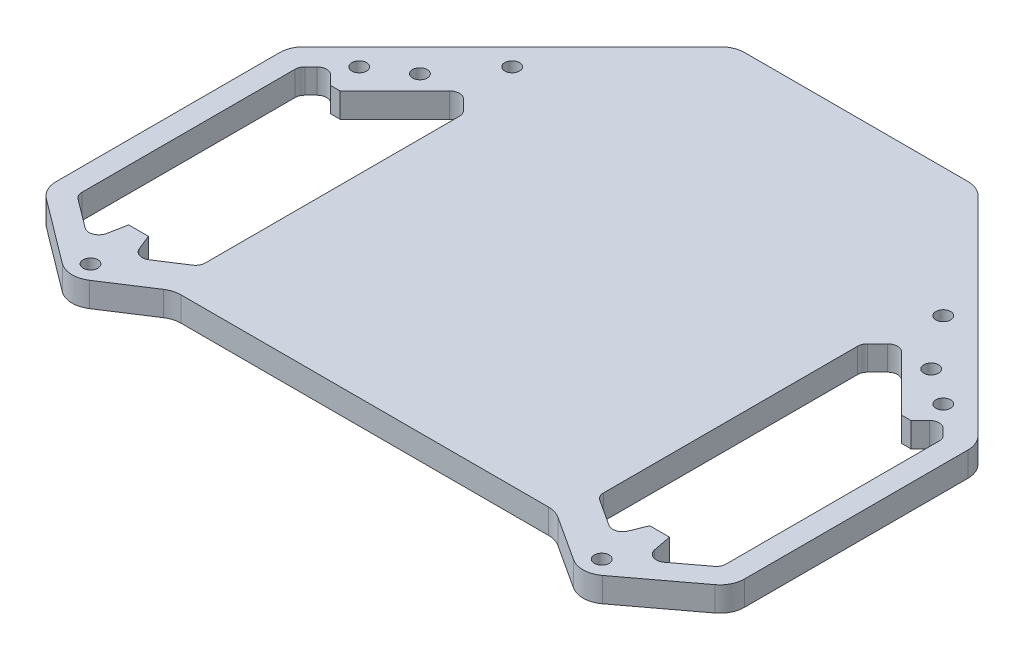
SolidWorks part; units mm, degrees
ref_plane "Front Plane" through (0, 0, 0) normal (0, 0, 1) x (1, 0, 0)
ref_plane "Top Plane" through (0, 0, 0) normal (0, 1, 0) x (1, 0, 0)
ref_plane "Right Plane" through (0, 0, 0) normal (1, 0, 0) x (0, 0, -1)
sketch "Sketch1" plane through (0, 0, 0) normal (0, 1, 0) x (1, 0, 0)
  line L0 (-52.1641, -38.6452) -> (-70, -25.2479)
  line L1 (-70, -25.2479) -> (-70, 24.7523)
  line L2 (-70, 24.7523) -> (-24.7523, 70)
  line L3 (-52.1641, -38.6452) -> (-38.8516, -30)
  line L4 (0, -30) -> (0, 70)
  line L5 (0, -30) -> (-38.8516, -30)
  line L6 (-59.397, 28.2843) -> (-43.8406, 43.8406) construction
  line L7 (-51.9976, -33.7676) -> (-63.9796, -15.3169) construction
  line L8 (-24.7523, 70) -> (0, 70)
  line L9 (0, 0) -> (-85, 0) construction
  line L10 (-43.8406, 43.8406) -> (0, 0) construction
  line L11 (-51.9976, -33.7676) -> (0, 0) construction
  line L12 (-59.0038, 22.1) -> (-57.096, 22.1)
  line L13 (-65.5, 22.1812) -> (-65.5, -23)
  line L14 (-55, -23) -> (-51, -23)
  line L15 (-40.5, 30.6005) -> (-40.5, -23)
  line L16 (-53, 22.1) -> (-53, -23) construction
  line L17 (-65.5, 22.1812) -> (-62.2925, 25.3887)
  line L18 (-62.2925, 25.3887) -> (-59.0038, 22.1)
  line L19 (-57.096, 22.1) -> (-44.5477, 34.6482)
  line L20 (-44.5477, 34.6482) -> (-40.5, 30.6005)
  line L21 (-65.5, -23) -> (-56.3366, -29.883)
  line L22 (-56.3366, -29.883) -> (-55, -23)
  line L23 (-51, -23) -> (-48.7962, -28.3876)
  line L24 (-48.7962, -28.3876) -> (-40.5, -23)
  circle A0 centre (0, 0) radius 85 construction
  circle A1 centre (-43.8406, 43.8406) radius 1.5
  circle A2 centre (-51.9976, -33.7676) radius 1.5
  circle A3 centre (-59.397, 28.2843) radius 1.5
  circle A4 centre (-63.9796, -15.3169) radius 1.5 construction
  circle A5 centre (-51.9976, 33.2324) radius 1.5
  dimension "D7" = 3
  dimension "D17" = 170
  dimension "D20" = 12.5
  dimension "D2" = 30
  dimension "D3" = 4
  dimension "D4" = 4
  dimension "D5" = 4.5
  dimension "D6" = 70
  dimension "D8" = 62
  dimension "D9" = 22
  dimension "D10" = 22
  dimension "D11" = 25
  dimension "D12" = 45.1
  dimension "D13" = 53
  dimension "D14" = 45
  dimension "D15" = 33
  dimension "D16" = 23
  dimension "D18" = 5
  dimension "D19" = 70
  dimension "D21" = 5
  dimension "D22" = 5
  dimension "D23" = 4
  dimension "D24" = 6
  dimension "D25" = 15
  dimension "D26" = 67
extrude "Boss-Extrude1" add sketch "Sketch1" along normal blind 5
fillet "Fillet1" radius 2 8 edges at (-40.5, 2.5, 23) (-48.7962, 2.5, 28.3876) (-56.3366, 2.5, 29.883) (-65.5, 2.5, 23) (-65.5, 2.5, -22.1812) (-62.2925, 2.5, -25.3887) (-40.5, 2.5, -30.6005) (-44.5477, 2.5, -34.6482)
mirror "Mirror1" about plane through (0, 5, 30) normal (-1, 0, 0) of "Fillet1", "Boss-Extrude1"
sketch "Sketch2" plane through (0, 0, 0) normal (0, 1, 0) x (1, 0, 0)
  line L0 (24.7523, 70) -> (-24.7523, 70) construction
  line L1 (-35, 70) -> (35, 70)
  line L2 (-35, 70) -> (-35, -27)
  line L3 (-35, -27) -> (35, -27)
  line L4 (35, 70) -> (35, -27)
  line L5 (-38.8516, -30) -> (38.8516, -30) construction
  dimension "D1" = 3
  dimension "D2" = 70
  dimension "D3" = 35
extrude "Cut-Extrude1" cut sketch "Sketch2" along normal blind 3
fillet "Fillet2" radius 5 10 edges at (-70, 2.5, 25.2479) (-70, 2.5, -24.7523) (-24.7523, 4, -70) (24.7523, 4, -70) (70, 2.5, -24.7523) (70, 2.5, 25.2479) (38.8516, 2.5, 30) (52.1641, 2.5, 38.6452) (-38.8516, 2.5, 30) (-52.1641, 2.5, 38.6452)
